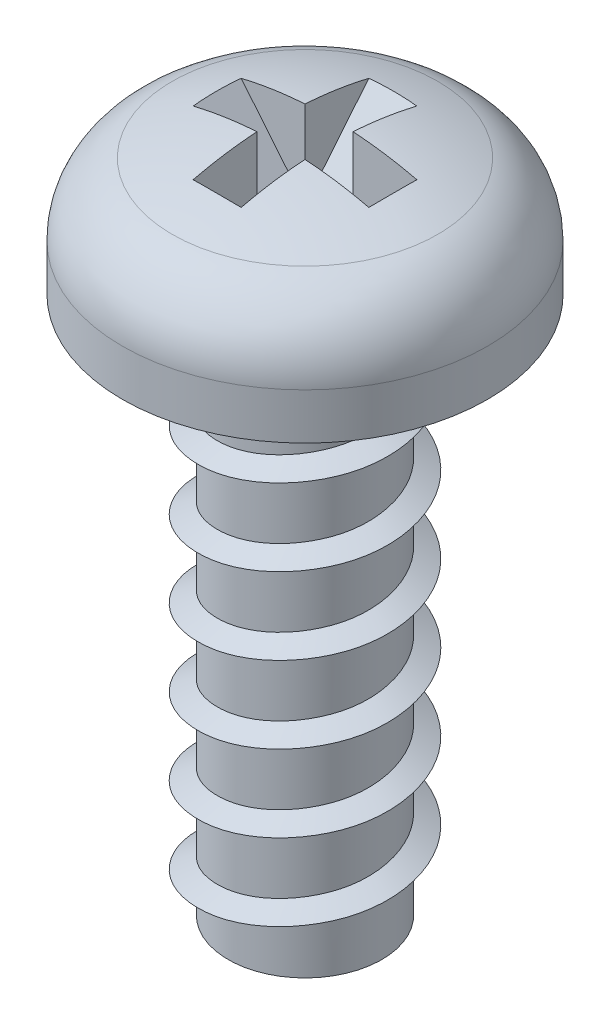
SolidWorks part; units mm, degrees
note: '?' marks a value the reader was unsure of.
ref_plane "Plan de face" through (0, 0, 0) normal (0, 0, 1) x (1, 0, 0)
ref_plane "Plan de dessus" through (0, 0, 0) normal (0, 1, 0) x (1, 0, 0)
ref_plane "Plan de droite" through (0, 0, 0) normal (1, 0, 0) x (0, 0, -1)
sketch "Esquisse1" plane through (0, 0, 0) normal (0, 0, 1) x (1, 0, 0)
  line L0 (0, 0) -> (0, 14.6029) construction
  line L1 (0, -14) -> (0, 3.7)
  line L2 (2, 0) -> (4.75, 0)
  line L3 (4.75, 0) -> (4.75, 1.2)
  line L4 (0, 3.7) -> (-69.7943, 3.7) construction
  line L5 (2, 0) -> (2, -14)
  line L6 (2, -14) -> (0, -14)
  arc A0 (0, 3.7) -> (3.454, 3.072) centre (0, -6.1125) cw
  arc A1 (4.75, 1.2) -> (3.454, 3.072) centre (2.75, 1.2) ccw
  dimension "D2" = 3.7
  dimension "D3" = 2
  dimension "D1" = 9.5
  dimension "D4" = 1.2
  dimension "D5" = 4
  dimension "D6" = 14
revolve "Révolution3" add sketch "Esquisse1" angle 360 about L0
sketch "Esquisse2" plane through (0, 0, 0) normal (0, 0, 1) x (1, 0, 0)
  line L0 (0, 3.7) -> (0, 1.2)
  line L1 (0.7731, 1.5657) -> (2.3, 3.4266)
  arc A0 (3.454, 3.072) -> (-3.454, 3.072) centre (0, -6.1125) ccw construction
  arc A1 (0, 1.2) -> (0.7731, 1.5657) centre (0, 2.2) ccw
  arc A2 (2.3, 3.4266) -> (0, 3.7) centre (0, -6.1125) ccw
  dimension "D1" = 2.5
  dimension "D3" = 1
  dimension "D2" = 2.3
extrude "Enlèv. mat.-Extru.1" cut sketch "Esquisse2" against normal mid plane 1.25
ref_axis "Axe1" through (0, 0, 0) along (0, -1, 0)?
pattern_circular "Répétition circulaire1" count 4 over 360 about axis through (0, 0, 0) along (0, 1, 0) of "Enlèv. mat.-Extru.1"
sketch "Esquisse3" plane through (0, 0, 0) normal (1, 0, 0) x (0, 0, -1)
  line L0 (2, -14) -> (2.5, -13.7113)
  line L1 (2.5, -13.7113) -> (2, -13.4226)
  line L2 (2, -14) -> (2, 0) construction
  line L3 (2, -13.4226) -> (2, -14)
  line L5 (0, 0) -> (0, -14) construction
  dimension "D1" = 2.5
  dimension "D2" = 60
sketch "Esquisse5" plane through (0, -14, 0) normal (0, -1, 0) x (1, 0, 0)
  circle A1 centre (0, 0) radius 2
  circle A2 centre (0, 0) radius 2 construction
  point P4 (0, 2)
curve "Hélice/Spirale1" pitch 2 height 14 turns 7
sweep "Balayage2" add profiles "Esquisse3" path "Hélice/Spirale1"
